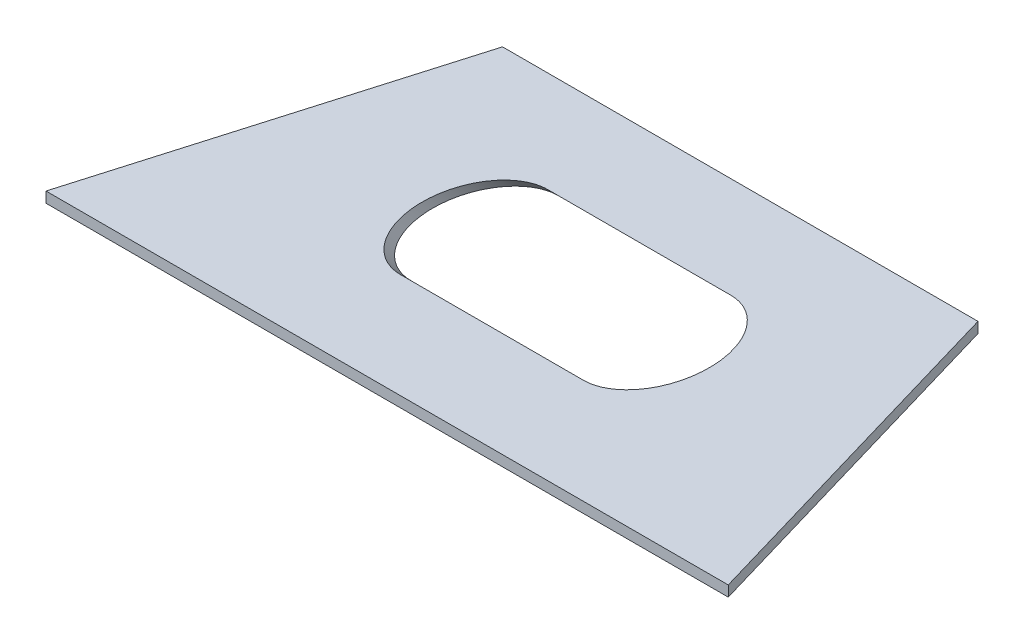
SolidWorks part; units mm, degrees
ref_plane "Front Plane" through (0, 0, 0) normal (0, 0, 1) x (1, 0, 0)
ref_plane "Top Plane" through (0, 0, 0) normal (0, 1, 0) x (1, 0, 0)
ref_plane "Right Plane" through (0, 0, 0) normal (1, 0, 0) x (0, 0, -1)
sketch "Sketch1" plane through (0, 0, 0) normal (0, 1, 0) x (1, 0, 0)
  line L0 (0, 0) -> (193.2, 0)
  line L3 (96.6, 0) -> (96.6, 100) construction
  line L5 (0, 0) -> (29.2799, 100)
  line L6 (193.2, 0) -> (163.9201, 100)
  line L7 (29.2799, 100) -> (163.9201, 100)
extrude "Boss-Extrude1" add sketch "Sketch1" along normal blind 3
sketch "Sketch2" plane through (0, 3, 0) normal (0, 1, 0) x (1, 0, 0)
  line L0 (163.9201, 100) -> (163.9201, 0) construction
  line L1 (0, 0) -> (193.2, 0) construction
sketch "Sketch3" plane through (0, 0, 0) normal (0, 0, 1) x (1, 0, 0)
  line L0 (163.9201, 3) -> (163.9201, 0)
  line L1 (0, 0) -> (193.2, 0) construction
ref_plane "Plane1" through (163.9201, 0, 0) normal (1, 0, 0) x (0, 0, -1)
sketch "Sketch4" plane through (163.9201, 0, 0) normal (1, 0, 0) x (0, 0, -1)
  line L0 (0, 3) -> (100.6736, 103.6736)
ref_plane "Plane2" through (0, 1.5, 1.5) normal (0, -0.7071, -0.7071) x (-1, 0, 0)
sketch "Sketch8" plane through (0, 1.5, 1.5) normal (0, -0.7071, -0.7071) x (-1, 0, 0)
  line L0 (-96.6, 2.1213) -> (-96.6, 143.2449) construction
  line L1 (0, 2.1213) -> (-193.2, 2.1213) construction
  line L2 (-122.5, 37.8633) -> (-70.7, 37.8633) construction
  line L3 (-122.5, 52.6133) -> (-70.7, 52.6133)
  line L4 (-122.5, 23.1133) -> (-70.7, 23.1133)
  arc A0 (-122.5, 52.6133) -> (-122.5, 23.1133) centre (-122.5, 37.8633) ccw
  arc A1 (-70.7, 23.1133) -> (-70.7, 52.6133) centre (-70.7, 37.8633) ccw
  point P6 (-96.6, 37.8633)
  point P11 (0, 0)
extrude "Cut-Extrude4" cut sketch "Sketch8" along normal through all
sketch "Sketch10" plane through (0, 3, 0) normal (0, 1, 0) x (1, 0, 0)
  line L0 (96.6, 29.6872) -> (96.6, 71.4065) construction
  line L1 (70.7, 29.6872) -> (122.5, 29.6872) construction
  line L2 (122.5, 71.4065) -> (70.7, 71.4065) construction
  line L4 (96.6, 50.5468) -> (55.95, 50.5468) construction
